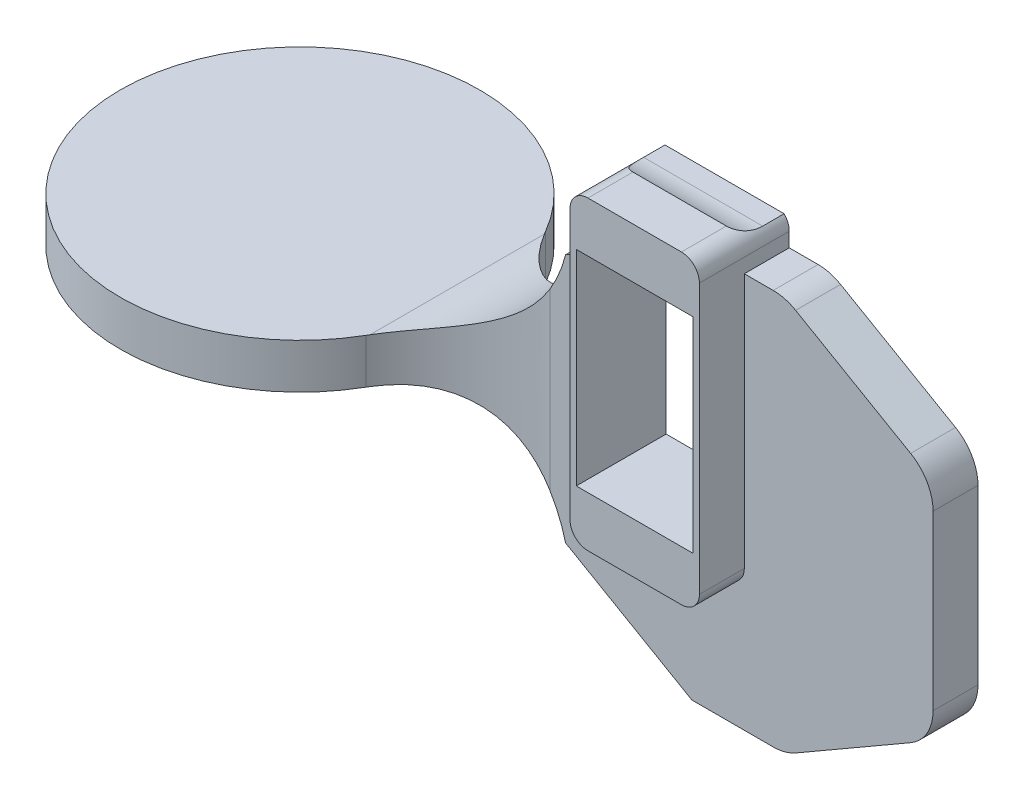
SolidWorks part; units mm, degrees
material "ABS"
ref_plane "Front Plane" through (0, 0, 0) normal (0, 0, 1) x (1, 0, 0)
ref_plane "Top Plane" through (0, 0, 0) normal (0, 1, 0) x (1, 0, 0)
ref_plane "Right Plane" through (0, 0, 0) normal (1, 0, 0) x (0, 0, -1)
other "Center of Mass"
sketch "Sketch1" plane through (0, 0, 0) normal (0, 1, 0) x (1, 0, 0)
  line L0 (0, 0) -> (128.1157, 0) construction
  line L2 (30.3109, -2.5) -> (82.5, -2.5)
  line L4 (30.3109, 2.5) -> (82.5, 2.5)
  line L5 (82.5, -2.5) -> (82.5, 2.5)
  arc A0 (17.3205, 10) -> (17.3205, -10) centre (0, 0) ccw
  arc A1 (30.3109, 2.5) -> (17.3205, 10) centre (30.3109, 17.5) cw
  arc A2 (17.3205, -10) -> (30.3109, -2.5) centre (30.3109, -17.5) cw
  point P3 (50, 0)
  dimension "D1" = 40
  dimension "D4" = 15
  dimension "D5" = 15
  dimension "D2" = 5
  dimension "D3" = 82.5
extrude "Boss-Extrude1" add sketch "Sketch1" along normal blind 5
sketch "Sketch4" plane through (82.5, 0, 0) normal (1, 0, 0) x (0, 0, -1)
  line L0 (0, 5) -> (0, 0) construction
  line L1 (-2.5, 5) -> (2.5, 5) construction
  line L3 (-2.5, -22.5) -> (2.5, -22.5)
  line L4 (-2.5, -22.5) -> (-2.5, 27.5)
  line L5 (-2.5, 27.5) -> (2.5, 27.5)
  line L6 (2.5, -22.5) -> (2.5, 27.5)
  line L7 (-2.5, -22.5) -> (2.5, 27.5) construction
  line L8 (-2.5, 27.5) -> (2.5, -22.5) construction
  point P5 (0, 2.5)
  dimension "D1" = 50
  dimension "D2" = 5
extrude "Boss-Extrude4" add sketch "Sketch4" against normal blind 50
fillet "Fillet1" radius 15 2 edges at (32.5, 0, 0) (32.5, 5, 0)
sketch "Sketch5" plane through (0, 0, 2.5) normal (0, 0, 1) x (1, 0, 0)
  line L0 (82.5, 2.5) -> (30.3109, 2.5) construction
  line L1 (82.5, 27.5) -> (82.5, -22.5) construction
  line L2 (30.3109, 12.1974) -> (30.3109, -7.1974) construction
  line L3 (57.5, 27.5) -> (57.5, -22.5) construction
  line L4 (32.5, 27.5) -> (82.5, 27.5) construction
  line L5 (32.5, -22.5) -> (82.5, -22.5) construction
  line L6 (56.4054, 2.5) -> (30.3109, 2.5) construction
  line L7 (32.5, 27.5) -> (32.5, 20) construction
  line L8 (32.5, 28.75) -> (57, 28.75)
  line L9 (32.5, 28.75) -> (32.5, -23.75)
  line L10 (32.5, -23.75) -> (57, -23.75)
  line L11 (57, 28.75) -> (57, -23.75)
  line L12 (32.5, 28.75) -> (57, -23.75) construction
  line L13 (32.5, -23.75) -> (57, 28.75) construction
  line L14 (44.75, -23.75) -> (44.75, 28.75) construction
  line L15 (38.25, -0.3) -> (51.25, 22.5) construction
  line L16 (38.25, 22.5) -> (51.25, 22.5)
  line L17 (38.25, 22.5) -> (38.25, -0.3)
  line L18 (38.25, -0.3) -> (51.25, -0.3)
  line L19 (51.25, 22.5) -> (51.25, -0.3)
  line L20 (38.25, 11.1) -> (51.25, 11.1) construction
  line L21 (51.95, -5.9) -> (37.55, -5.9)
  line L22 (51.95, -5.9) -> (51.95, 28.1)
  line L23 (51.95, 28.1) -> (37.55, 28.1)
  line L24 (37.55, -5.9) -> (37.55, 28.1)
  line L25 (51.95, -5.9) -> (37.55, 28.1) construction
  line L26 (51.95, 28.1) -> (37.55, -5.9) construction
  circle A0 centre (44.75, 16.5) radius 12.25
  circle A1 centre (44.75, -11.5) radius 12.25
  circle A2 centre (44.75, -11.5) radius 15.75
  circle A3 centre (64.9562, -2.7988) radius 1.5
  circle A4 centre (64.9562, -2.7988) radius 3
  circle A5 centre (64.9562, 7.7988) radius 3
  circle A6 centre (64.9562, 7.7988) radius 1.5
  circle A7 centre (44.75, -11.5) radius 1.5
  circle A8 centre (44.75, -11.5) radius 3
  point P13 (44.75, 2.5)
  point P30 (44.75, 11.1)
  dimension "D4" = 12.25
  dimension "D5" = 24.5
  dimension "D13" = 31.5
  dimension "D14" = 3
  dimension "D16" = 6
  dimension "D17" = 22
  dimension "D18" = 3
  dimension "D19" = 6
  dimension "D1" = 24.5
  dimension "D2" = 52.5
  dimension "D3" = 0
  dimension "D6" = 12.25
  dimension "D7" = 6
  dimension "D8" = 22.8
  dimension "D9" = 13
  dimension "D10" = 34
  dimension "D11" = 14.4
  dimension "D12" = 5.6
  dimension "D15" = 5.2988
sketch "Sketch6" plane through (0, 0, 2.5) normal (0, 0, 1) x (1, 0, 0)
  circle A0 centre (44.75, -11.5) radius 1.5
  dimension "D1" = 3
sketch "Sketch8" plane through (0, 0, 2.5) normal (0, 0, 1) x (1, 0, 0)
  line L0 (37.55, -5.9) -> (37.55, 28.1)
  line L1 (37.55, 28.1) -> (51.95, 28.1)
  line L2 (51.95, 28.1) -> (51.95, -5.9)
  line L3 (51.95, -5.9) -> (37.55, -5.9)
  dimension "D1" = 34
extrude "Boss-Extrude5" add sketch "Sketch8" along normal blind 5
sketch "Sketch9" plane through (0, 0, 7.5) normal (0, 0, 1) x (1, 0, 0)
  line L0 (38.25, 22.5) -> (51.25, 22.5)
  line L1 (51.25, 22.5) -> (51.25, -0.3)
  line L2 (51.25, -0.3) -> (38.25, -0.3)
  line L3 (38.25, -0.3) -> (38.25, 22.5)
extrude "Cut-Extrude2" cut sketch "Sketch9" against normal through all
fillet "Fillet2" radius 5 2 edges at (32.5, -22.5, 0) (32.5, 27.5, 0)
fillet "Fillet3" radius 2 4 edges at (51.95, -5.9, 5) (51.95, 28.1, 5) (37.55, 28.1, 5) (37.55, -5.9, 5)
fillet "Fillet4" radius 6 1 edges at (44.75, 27.5, 2.5)
sketch "Sketch14" plane through (0, 0, 2.5) normal (0, 0, 1) x (1, 0, 0)
  line L0 (72.9562, 27.5) -> (72.9562, -22.5)
  line L1 (82.5, -22.5) -> (28.5, -22.5)
  line L2 (82.5, -22.5) -> (82.5, -19.5)
  line L3 (56.5017, -19.5) -> (28.5, -19.5)
  line L4 (28.5, -22.5) -> (28.5, -19.5)
  line L5 (51.3783, 27.5) -> (82.5, 27.5) construction
  line L6 (56.5017, 24.5) -> (28.5, 24.5)
  line L7 (82.5, 2.5) -> (17.3205, 2.5) construction
  line L8 (17.3205, 5) -> (17.3205, 0) construction
  line L9 (51.3055, 27.5) -> (29.6549, 15)
  line L10 (29.6549, 15) -> (29.6549, -10)
  line L11 (29.6549, -10) -> (51.3055, -22.5)
  line L12 (51.3055, -22.5) -> (72.9562, -10)
  line L13 (72.9562, -10) -> (72.9562, 15)
  line L14 (72.9562, 15) -> (51.3055, 27.5)
  circle A0 centre (51.3055, 2.5) radius 21.6506 construction
  circle A1 centre (64.9562, 7.7988) radius 3 construction
  line M5 (32.5, -15) -> (32.5, -17.5)
  arc M6 (32.5, -17.5) -> (37.5, -22.5) centre (37.5, -17.5) ccw
  line M7 (37.5, -22.5) -> (82.5, -22.5)
  line M8 (82.5, -22.5) -> (82.5, 27.5)
  line M9 (82.5, 27.5) -> (51.3783, 27.5)
  arc M10 (51.3783, 27.5) -> (51.95, 26.1) centre (49.95, 26.1) cw
  line M11 (51.95, 26.1) -> (51.95, -3.9)
  line M15 (37.55, -3.9) -> (37.55, 26.1)
  arc M16 (37.55, 26.1) -> (38.1217, 27.5) centre (39.55, 26.1) cw
  line M17 (38.1217, 27.5) -> (37.5, 27.5)
  arc M18 (37.5, 27.5) -> (32.5, 22.5) centre (37.5, 22.5) ccw
  line M19 (32.5, 22.5) -> (32.5, 20)
  arc M20 (32.5, 20) -> (30.3109, 12.1974) centre (17.5, 20) cw
  arc M24 (30.3109, -7.1974) -> (32.5, -15) centre (17.5, -15) cw
  dimension "D4" = 8
  dimension "D6" = 25
  dimension "D1" = 3
  dimension "D2" = 8
  dimension "D3" = 54
  dimension "D5" = 0
extrude "Cut-Extrude6" cut sketch "Sketch14" against normal blind 10 contours L11 L3 M24 M5 M6 | L11 L3 M6 M7 | L12 L1 L0 | L11 L12 L3 | L0 M9 M7 M8 | L14 L0 M9 M10 | L6 L14 M10 M11 | L9 L6 M15 M18 M19 M20 | L6 M15 M16 M17 M18 region at (77.7281, 2.5, 2.5) region at (65.7396, 23.3332, 2.5) region at (65.7393, -18.3333, 2.5) region at (53.4314, 25.4107, 2.5) region at (51.3055, -20.5, 2.5) region at (41.4922, -21.0298, 2.5) region at (37.0179, -16.8305, 2.5) region at (34.8161, 21.1656, 2.5) region at (35.7594, 25.7757, 2.5)
fillet "Fillet5" radius 5 4 edges at (56.5017, 24.5, 0) (72.9562, 15, 0) (72.9562, -10, 0) (56.5017, -19.5, 0)
